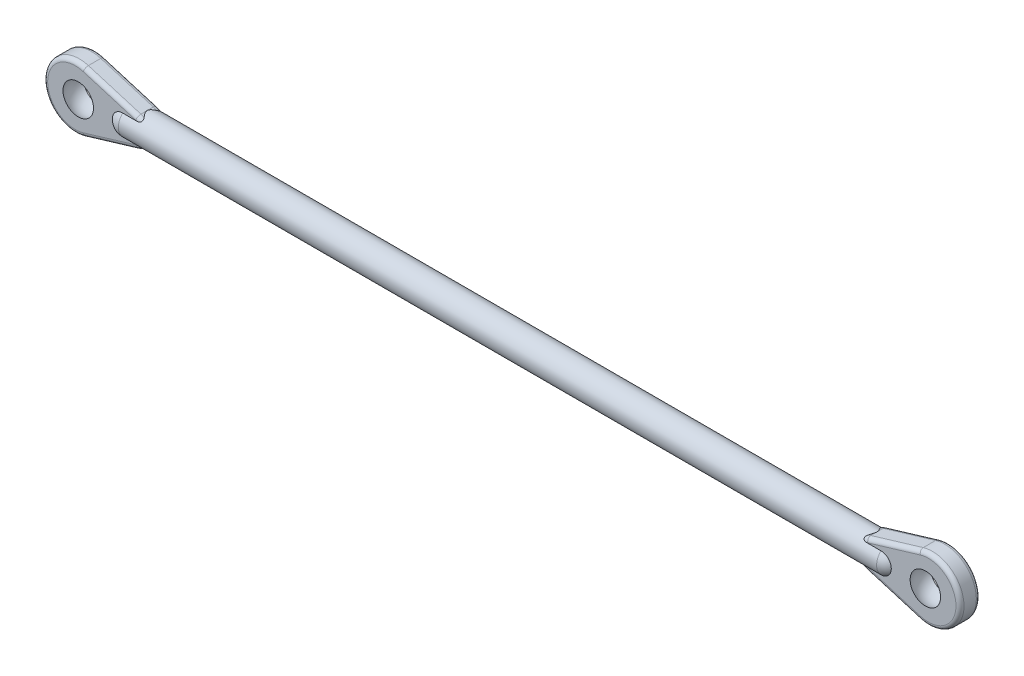
SolidWorks part; units mm, degrees
ref_plane "Front Plane" through (0, 0, 0) normal (0, 0, 1) x (1, 0, 0)
ref_plane "Top Plane" through (0, 0, 0) normal (0, 1, 0) x (1, 0, 0)
ref_plane "Right Plane" through (0, 0, 0) normal (1, 0, 0) x (0, 0, -1)
sketch "Sketch1" plane through (0, 0, 0) normal (1, 0, 0) x (0, 0, -1)
  circle A0 centre (0, 0) radius 2.4257
  dimension "D1" = 4.8514
extrude "Boss-Extrude1" add sketch "Sketch1" along normal mid plane 131.445
fillet "Fillet1" radius 2.4257 2 edges at (-65.7225, 0, -2.4257) (65.7225, 0, -2.4257)
sketch "Sketch2" plane through (0, 0, 0) normal (0, 0, 1) x (1, 0, 0)
  line L0 (0, -2.4257) -> (0, 2.4257) construction
  line L1 (-63.2968, -2.4257) -> (63.2968, -2.4257) construction
  line L2 (63.2968, 2.4257) -> (-63.2968, 2.4257) construction
  line L3 (60.9219, 2.4257) -> (69.6887, 5.0597)
  line L4 (60.9219, -2.4257) -> (69.6887, -5.0597)
  line L5 (65.3053, 3.7427) -> (65.3053, -3.7427) construction
  line L6 (73.7743, 0) -> (67.6529, 0)
  line L7 (-65.3053, 3.7427) -> (-65.3053, -3.7427) construction
  line L8 (-73.7743, 0) -> (-67.6529, 0)
  line L9 (-60.9219, -2.4257) -> (-69.6887, -5.0597)
  line L10 (-60.9219, 2.4257) -> (-69.6887, 5.0597)
  line L11 (60.9219, 2.4257) -> (60.9219, -2.4257) construction
  line L12 (-60.9219, 2.4257) -> (-60.9219, -2.4257) construction
  arc A0 (69.6887, 5.0597) -> (69.6887, -5.0597) centre (71.2089, 0) cw
  circle A1 centre (70.7136, 0) radius 3.0607
  arc A2 (60.9219, 2.4257) -> (60.9219, -2.4257) centre (61.6507, 0) ccw
  arc A3 (-60.9219, 2.4257) -> (-60.9219, -2.4257) centre (-61.6507, 0) cw
  circle A4 centre (-70.7136, 0) radius 3.0607
  arc A5 (-69.6887, 5.0597) -> (-69.6887, -5.0597) centre (-71.2089, 0) ccw
  circle A6 centre (70.7136, 0) radius 1.905 construction
  circle A7 centre (-70.7136, 0) radius 1.905 construction
  point P10 (65.3053, 0)
  dimension "D1" = 152.9842
  dimension "D2" = 145.2372
  dimension "D3" = 3.81
  dimension "D4" = 6.1214
  dimension "D5" = 121.8438
  dimension "D6" = 5.2832
extrude "Boss-Extrude2" add sketch "Sketch2" along normal mid plane 3.4036 contours A4 L8 | A4 L8 | L10 A5 L9 A3 A4 | L3 A2 L4 A0 A1 | L6 A1 | L6 A1 region at (65.3638, 3.548, 0) region at (70.7136, -1.299, 0) region at (70.7136, 1.299, 0) region at (-70.7136, 1.299, 0) region at (-70.7136, -1.299, 0) region at (-65.3638, -3.548, 0)
revolve "Cut-Revolve1" cut sketch "Sketch2<4>" angle 360 about L6 region at (70.7136, -1.299, 0) region at (-70.7136, -1.299, 0)
sketch "Sketch2<4>" plane through (0, 0, 0) normal (0, 0, 1) x (1, 0, 0) same geometry as "Sketch2"
fillet "Fillet2" radius 0.6731 20 edges at (60.3144, 2.1516, -1.7018) (65.3053, 3.7427, -1.7018) (60.3144, -2.1516, -1.7018) (65.3053, -3.7427, -1.7018) (60.3144, 2.1516, 1.7018) (65.3053, 3.7427, 1.7018) (60.3144, -2.1516, 1.7018) (65.3053, -3.7427, 1.7018) (-60.3144, 2.1516, -1.7018) (-65.3053, 3.7427, -1.7018) (-60.3144, -2.1516, -1.7018) (-65.3053, -3.7427, -1.7018) (-60.3144, 2.1516, 1.7018) (-65.3053, 3.7427, 1.7018) (-60.3144, -2.1516, 1.7018) (-65.3053, -3.7427, 1.7018) (76.4921, 0, -1.7018) (76.4921, 0, 1.7018) (-76.4921, 0, -1.7018) (-76.4921, 0, 1.7018)
